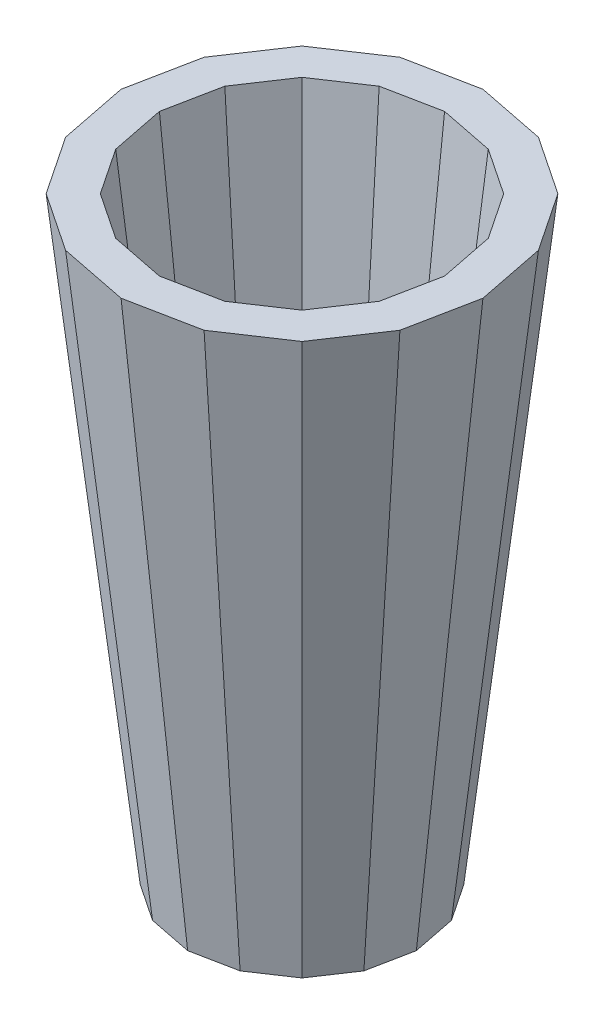
SolidWorks part; units mm, degrees
ref_plane "Front" through (0, 0, 0) normal (0, 0, 1) x (1, 0, 0)
ref_plane "Top" through (0, 0, 0) normal (0, 1, 0) x (1, 0, 0)
ref_plane "Right" through (0, 0, 0) normal (1, 0, 0) x (0, 0, -1)
sketch "Sketch1" plane through (0, 0, 0) normal (0, 1, 0) x (1, 0, 0)
  line L1 (120.4314, 0) -> (111.2641, 46.0871)
  line L2 (111.2641, 46.0871) -> (85.1579, 85.1579)
  line L3 (85.1579, 85.1579) -> (46.0871, 111.2641)
  line L4 (46.0871, 111.2641) -> (0, 120.4314)
  line L5 (0, 120.4314) -> (-46.0871, 111.2641)
  line L6 (-46.0871, 111.2641) -> (-85.1579, 85.1579)
  line L7 (-85.1579, 85.1579) -> (-111.2641, 46.0871)
  line L8 (-111.2641, 46.0871) -> (-120.4314, 0)
  line L9 (-120.4314, 0) -> (-111.2641, -46.0871)
  line L10 (-111.2641, -46.0871) -> (-85.1579, -85.1579)
  line L11 (-85.1579, -85.1579) -> (-46.0871, -111.2641)
  line L12 (-46.0871, -111.2641) -> (0, -120.4314)
  line L13 (0, -120.4314) -> (46.0871, -111.2641)
  line L14 (46.0871, -111.2641) -> (85.1579, -85.1579)
  line L15 (85.1579, -85.1579) -> (111.2641, -46.0871)
  line L16 (111.2641, -46.0871) -> (120.4314, 0)
  circle A0 centre (0, 0) radius 118.1173 construction
  dimension "D1" = 46.99
ref_plane "Plane1" through (0, -558.8, 0) normal (0, 1, 0) x (1, 0, 0)
sketch "Sketch2" plane through (0, -558.8, 0) normal (0, 1, 0) x (1, 0, 0)
  line L1 (58.2696, 0) -> (53.8341, 22.2988)
  line L2 (53.8341, 22.2988) -> (41.2029, 41.2029)
  line L3 (41.2029, 41.2029) -> (22.2988, 53.8341)
  line L4 (22.2988, 53.8341) -> (0, 58.2696)
  line L5 (0, 58.2696) -> (-22.2988, 53.8341)
  line L6 (-22.2988, 53.8341) -> (-41.2029, 41.2029)
  line L7 (-41.2029, 41.2029) -> (-53.8341, 22.2988)
  line L8 (-53.8341, 22.2988) -> (-58.2696, 0)
  line L9 (-58.2696, 0) -> (-53.8341, -22.2988)
  line L10 (-53.8341, -22.2988) -> (-41.2029, -41.2029)
  line L11 (-41.2029, -41.2029) -> (-22.2988, -53.8341)
  line L12 (-22.2988, -53.8341) -> (0, -58.2696)
  line L13 (0, -58.2696) -> (22.2988, -53.8341)
  line L14 (22.2988, -53.8341) -> (41.2029, -41.2029)
  line L15 (41.2029, -41.2029) -> (53.8341, -22.2988)
  line L16 (53.8341, -22.2988) -> (58.2696, 0)
  circle A0 centre (0, 0) radius 57.15 construction
  dimension "D1" = 114.3
loft "Loft1" add profiles "Sketch1", "Sketch2"
shell "Shell1" thickness 19.05 removed face at (0, -558.8, 0) removed face at (0, 0, 0)
ref_plane "Plane2" through (0, -228.6, 0) normal (0, 1, 0) x (1, 0, 0)
sketch "Sketch3" plane through (0, 0, 0) normal (0, 0, 1) x (1, 0, 0)
  line L0 (-85.1579, 0) -> (-111.2641, 0) construction
  line L1 (-81.4638, -177.8) -> (-30.6638, -177.8)
  line L2 (-81.4638, -177.8) -> (-81.4638, -228.6)
  line L3 (-81.4638, -228.6) -> (-30.6638, -228.6)
  line L5 (-30.6638, -177.8) -> (-30.6638, -228.6)
  dimension "D1" = 50.8
  dimension "D2" = 228.6
extrude "Boss-Extrude1" add sketch "Sketch3" against normal blind 35.56
sketch "Sketch4" plane through (0, -228.6, 0) normal (0, 1, 0) x (1, 0, 0)
  circle A0 centre (0, 0) radius 98.9543 construction
sketch "Sketch5" plane through (0, -558.8, 0) normal (0, 1, 0) x (1, 0, 0)
  circle A0 centre (0, 0) radius 16.7949 construction
ref_axis "Axis1" through (0, -558.8, 0) along (0, 1, 0)
pattern_circular "CirPattern1" count 16 over 360 about axis through (0, -558.8, 0) along (0, 1, 0) of "Boss-Extrude1"
sketch "Sketch6" plane through (0, 0, 0) normal (0, 0, 1) x (1, 0, 0)
  line L0 (-81.1142, -177.8) -> (-74.9397, -177.8) construction
  line L1 (98.9543, -228.6) -> (-98.9543, -228.6) construction
  line L2 (-30.6638, -228.6) -> (-30.6638, -177.8) construction
  line L3 (0, -222.0665) -> (0, -183.1987) construction
  line L4 (0, -228.6) -> (0, -177.8) construction
  line L5 (0, -228.6) -> (0, -177.8) construction
  line L6 (-81.1142, -177.8) -> (-12.7014, -177.8)
  line L7 (-12.7014, -177.8) -> (-12.7014, -228.6)
  line L8 (-12.7014, -228.6) -> (-30.6638, -228.6)
  arc A0 (-81.1142, -177.8) -> (-30.6638, -228.6) centre (-17.5006, -165.0758) ccw
revolve "Cut-Revolve1" cut sketch "Sketch6" angle 360 about L3
sketch "Sketch8" plane through (0, -228.6, 0) normal (0, 1, 0) x (1, 0, 0)
  circle A0 centre (0, 0) radius 38.1
  dimension "D1" = 76.2
extrude "Cut-Extrude1" cut sketch "Sketch8" along normal up to next
fillet "Fillet1" radius 25.4 1 edges at (0, -228.6, 38.1)
sketch "Sketch9" plane through (0, -228.6, 0) normal (0, 1, 0) x (1, 0, 0)
  circle A0 centre (0, 0) radius 186.9833
extrude "Cut-Extrude2" cut sketch "Sketch9" along normal through all and the other way offset from surface 304.8 other way up to face at (0, -558.8, 0)
